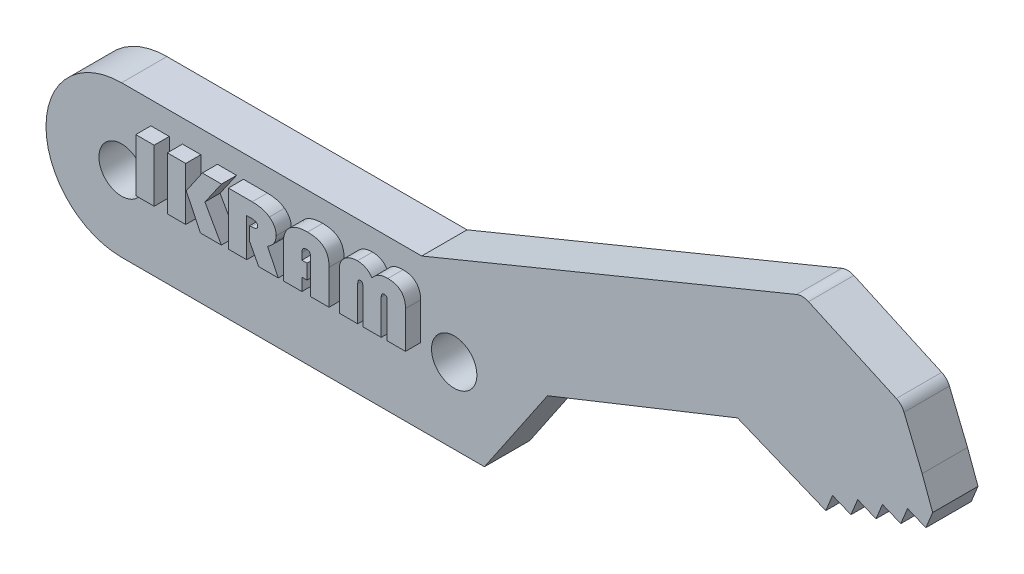
SolidWorks part; units mm, degrees
ref_plane "Front Plane" through (0, 0, 0) normal (0, 0, 1) x (1, 0, 0)
ref_plane "Top Plane" through (0, 0, 0) normal (0, 1, 0) x (1, 0, 0)
ref_plane "Right Plane" through (0, 0, 0) normal (1, 0, 0) x (0, 0, -1)
sketch "Sketch1" plane through (0, 0, 0) normal (0, 0, 1) x (1, 0, 0)
  line L0 (0, 0) -> (22, 0) construction
  line L1 (0, 5) -> (19.85, 5)
  line L2 (0, -5) -> (22, -5)
  line L3 (19.85, 5) -> (44.6431, 15.1937)
  line L4 (45.4379, 15.1788) -> (51.2451, 12.5335)
  line L5 (51.7554, 12.0038) -> (52.955, 9.0863)
  line L6 (24, -5) -> (22, -5)
  line L7 (24, -5) -> (28.1744, 1.1586)
  line L8 (28.1744, 1.1586) -> (40.742, 6.17)
  line L9 (40.742, 6.17) -> (46.5818, 3.7797)
  line L10 (46.5818, 3.7797) -> (47.0288, 4.8718)
  line L11 (47.0288, 4.8718) -> (48.2418, 4.3753)
  line L12 (48.2418, 4.3753) -> (48.6888, 5.4674)
  line L13 (48.6888, 5.4674) -> (49.9018, 4.9709)
  line L14 (49.9018, 4.9709) -> (50.3274, 6.0107)
  line L15 (50.3274, 6.0107) -> (51.5404, 5.5142)
  line L16 (51.5404, 5.5142) -> (51.9874, 6.6063)
  line L17 (51.9874, 6.6063) -> (53.2004, 6.1098)
  line L18 (53.2004, 6.1098) -> (53.6474, 7.2018)
  line L19 (53.6474, 7.2018) -> (52.955, 9.0863)
  arc A0 (0, 5) -> (0, -5) centre (0, 0) ccw
  circle A2 centre (0, 0) radius 1.5
  circle A3 centre (22, 0) radius 1.5
  arc A4 (51.2451, 12.5335) -> (51.7554, 12.0038) centre (50.8306, 11.6235) cw
  arc A5 (44.6431, 15.1937) -> (45.4379, 15.1788) centre (45.0233, 14.2688) cw
  point P3 (11, 0)
  point P18 (51.605, 12.3696)
  point P21 (45.0437, 15.3584)
  point P22 (24, -5)
  dimension "D3" = 3
  dimension "D4" = 3
  dimension "D12" = 1
  dimension "D2" = 5
  dimension "D5" = 19.85
  dimension "D6" = 157.65
  dimension "D7" = 27.24
  dimension "D8" = 133.16
  dimension "D9" = 7.21
  dimension "D10" = 136.84
  dimension "D11" = 3.55
  dimension "D13" = 24
  dimension "D14" = 55.87
  dimension "D15" = 7.44
  dimension "D16" = 214.13
  dimension "D17" = 13.53
  dimension "D18" = 224
  dimension "D19" = 6.31
  dimension "D20" = 1.18
  dimension "D21" = 1.66
  dimension "D22" = 2.0076
  dimension "D23" = 10
  dimension "D24" = 22
extrude "Boss-Extrude1" add sketch "Sketch1" along normal blind 3
sketch "Sketch6" plane through (0, 0, 3) normal (0, 0, 1) x (1, 0, 0)
  line L0 (1.5, 0) -> (20.5, 0) construction
  circle A2 centre (0, 0) radius 1.5 construction
  circle A3 centre (22, 0) radius 1.5 construction
  text T0 "IKRAM" font "Bauhaus 93" height 3.5
  dimension "D1" = 19
extrude "Boss-Extrude4" add sketch "Sketch6" along normal blind 1
